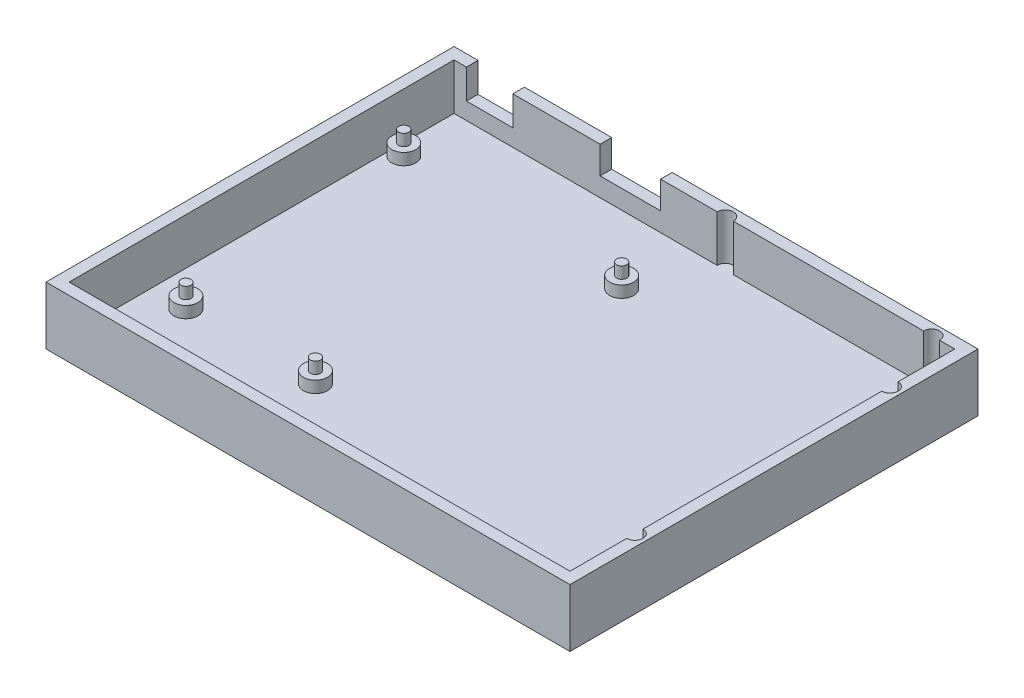
SolidWorks part; units mm, degrees
ref_plane "Front" through (0, 0, 0) normal (0, 0, 1) x (1, 0, 0)
ref_plane "Top" through (0, 0, 0) normal (0, 1, 0) x (1, 0, 0)
ref_plane "Right" through (0, 0, 0) normal (1, 0, 0) x (0, 0, -1)
sketch "Sketch1" plane through (0, 0, 0) normal (0, 1, 0) x (1, 0, 0)
  line L0 (-2.5, -2.5) -> (-2.5, 85.5)
  line L1 (0, 0) -> (108, 0)
  line L2 (0, 0) -> (0, 83)
  line L3 (0, 83) -> (108, 83)
  line L4 (108, 0) -> (108, 83)
  line L5 (-2.5, 85.5) -> (110.5, 85.5)
  line L6 (110.5, -2.5) -> (110.5, 85.5)
  line L7 (-2.5, -2.5) -> (110.5, -2.5)
  dimension "D1" = 108
  dimension "D2" = 83
  dimension "D3" = 2.5
extrude "Boss-Extrude1" add sketch "Sketch1" along normal blind 2.5 contours L5 L6 L7 L0
extrude "Boss-Extrude2" add sketch "Sketch1<3>" along normal offset from surface (12.5 mm away) 10 contours L0 L7 L6 L5 L4 L1 L2 L3 region at (-1.0678, 0, -41.5) offset beyond the face yes
sketch "Sketch1<3>" plane through (0, 0, 0) normal (0, 1, 0) x (1, 0, 0) same geometry as "Sketch1"
sketch "Sketch2" plane through (0, 0, -85.5) normal (0, 0, -1) x (-1, 0, 0)
  line L0 (-110.5, 12.5) -> (2.5, 12.5) construction
  line L1 (-12.175, 6.65) -> (-3.175, 6.65) construction
  line L2 (-12.175, 6.65) -> (-12.175, 12.5) construction
  line L3 (-12.175, 12.5) -> (-3.175, 12.5) construction
  line L4 (-3.175, 6.65) -> (-3.175, 12.5) construction
  line L5 (-3.175, 6.65) -> (-3.175, 17.15) construction
  line L8 (-44.04, 7.08) -> (-44.04, 12.5) construction
  line L9 (-44.04, 12.5) -> (-32, 12.5) construction
  line L10 (-32, 7.08) -> (-32, 12.5) construction
  line L12 (-44.04, 7.08) -> (-32, 7.08) construction
  line L13 (-44.04, 7.08) -> (-32, 7.08) construction
  line L14 (-44.54, 12.5) -> (-31.5, 12.5)
  line L15 (-44.54, 12.5) -> (-44.54, 6.58)
  line L16 (-44.54, 6.58) -> (-31.5, 6.58)
  line L17 (-31.5, 6.58) -> (-31.5, 12.5)
  line L18 (-12.675, 12.5) -> (-12.675, 6.15)
  line L19 (-12.675, 6.15) -> (-2.675, 6.15)
  line L20 (-44.04, 7.08) -> (-44.54, 7.08) construction
  line L21 (-44.04, 7.08) -> (-44.04, 6.58) construction
  line L22 (-32, 7.08) -> (-31.5, 7.08) construction
  line L23 (-32, 7.08) -> (-32, 6.58) construction
  line L24 (-2.675, 6.15) -> (-2.675, 12.5)
  line L25 (-2.675, 12.5) -> (-12.675, 12.5)
  line L26 (-12.175, 6.65) -> (-12.675, 6.65) construction
  line L27 (-12.175, 6.15) -> (-12.175, 6.65) construction
  line L28 (-3.175, 6.15) -> (-3.175, 6.65) construction
  line L29 (-3.175, 6.65) -> (-2.675, 6.65) construction
  dimension "D1" = 0.5
  dimension "D2" = 0.5
extrude "Cut-Extrude4" cut sketch "Sketch2" against normal up to surface (2.5 mm away)
sketch "Sketch4" plane through (0, 2.5, 0) normal (0, 1, 0) x (1, 0, 0)
  circle A0 centre (35.56, 17.555) radius 1.5875 construction
  circle A1 centre (7.62, 17.555) radius 1.5875 construction
  circle A2 centre (50.8, 68.355) radius 1.5875 construction
  circle A3 centre (2.54, 69.625) radius 1.5875 construction
  circle A4 centre (35.56, 17.555) radius 1.5875 construction
  circle A5 centre (7.62, 17.555) radius 1.5875 construction
  circle A6 centre (50.8, 68.355) radius 1.5875 construction
  circle A7 centre (2.54, 69.625) radius 1.5875 construction
  circle A8 centre (2.54, 69.625) radius 2.5875
  circle A9 centre (50.8, 68.355) radius 2.5875
  circle A10 centre (7.62, 17.555) radius 2.5875
  circle A11 centre (35.56, 17.555) radius 2.5875
  circle A12 centre (2.54, 69.625) radius 1.0875
  circle A13 centre (50.8, 68.355) radius 1.0875
  circle A14 centre (7.62, 17.555) radius 1.0875
  circle A15 centre (35.56, 17.555) radius 1.0875
  dimension "D1" = 1
  dimension "D2" = 0.5
extrude "Boss-Extrude5" add sketch "Sketch4" along normal blind 2.5 contours A10 | A11 | A9 | A8
extrude "Boss-Extrude6" add sketch "Sketch4<4>" along normal blind 5 contours A14 | A15 | A13 | A12
sketch "Sketch4<4>" plane through (0, 2.5, 0) normal (0, 1, 0) x (1, 0, 0) same geometry as "Sketch4"
sketch "Sketch5" plane through (0, 12.5, 0) normal (0, 1, 0) x (1, 0, 0)
  line L0 (108, 83) -> (44.54, 83) construction
  line L1 (101.25, 83) -> (104.75, 83)
  line L2 (56.75, 83) -> (60.25, 83)
  line L3 (108, 83) -> (108, 0) construction
  line L4 (108, 70.75) -> (108, 67.25)
  line L5 (108, 15.75) -> (108, 12.25)
  arc A0 (101.25, 83) -> (104.75, 83) centre (103, 83) cw
  arc A1 (56.75, 83) -> (60.25, 83) centre (58.5, 83) cw
  arc A2 (108, 70.75) -> (108, 67.25) centre (108, 69) cw
  arc A3 (108, 15.75) -> (108, 12.25) centre (108, 14) cw
  point P5 (53.5, 83)
  dimension "D1" = 1.75
  dimension "D4" = 5
  dimension "D5" = 14
  dimension "D2" = 5
  dimension "D3" = 54.5
  dimension "D6" = 14
extrude "Cut-Extrude5" cut sketch "Sketch5" against normal up to surface (10 mm away)
